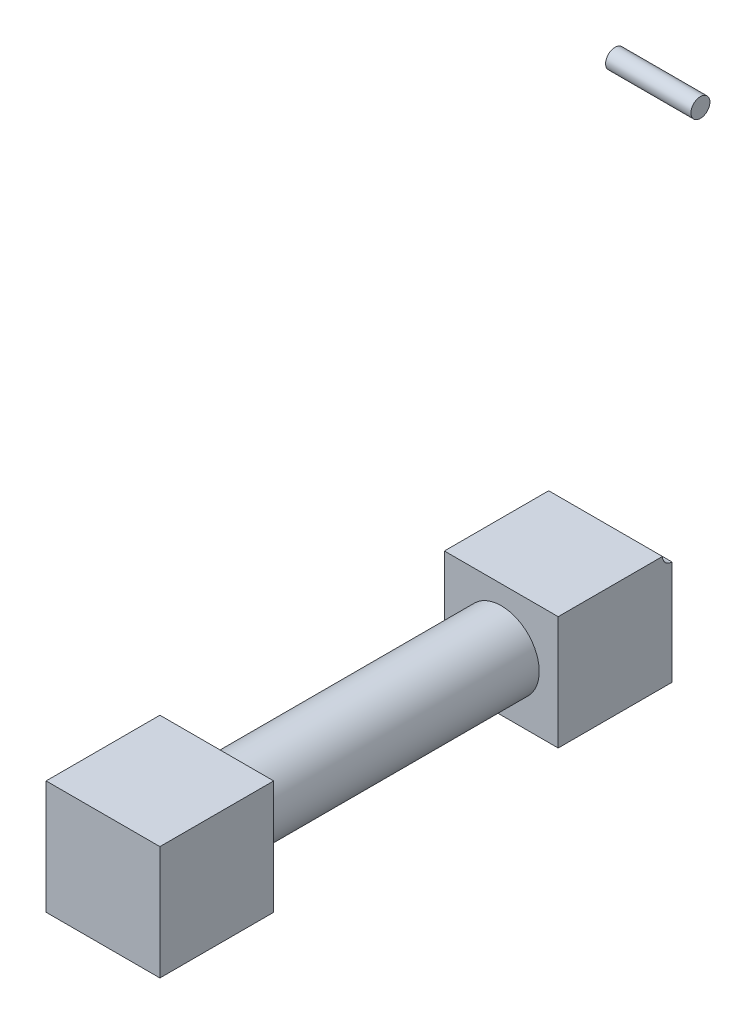
SolidWorks part; units mm, degrees
ref_plane "前视基准面" through (0, 0, 0) normal (0, 0, 1) x (1, 0, 0)
ref_plane "上视基准面" through (0, 0, 0) normal (0, 1, 0) x (1, 0, 0)
ref_plane "右视基准面" through (0, 0, 0) normal (1, 0, 0) x (0, 0, -1)
other "Configuration Table"
sketch "Sketch1" plane through (0, 0, 0) normal (0, 0, 1) x (1, 0, 0)
  line L1 (-30, -30) -> (30, -30)
  line L2 (-30, -30) -> (-30, 30)
  line L3 (-30, 30) -> (30, 30)
  line L4 (30, -30) -> (30, 30)
  line L5 (-30, -30) -> (30, 30) construction
  line L6 (-30, 30) -> (30, -30) construction
  point P0 (0, 0)
extrude "Boss-Extrude1" add sketch "Sketch1" along normal blind 60
ref_plane "Plane1" through (0, 0, 60) normal (0, 0, 1) x (1, 0, 0)
sketch "Sketch2" plane through (0, 0, 60) normal (0, 0, 1) x (1, 0, 0)
  circle A0 centre (0, 0) radius 20
extrude "Boss-Extrude2" add sketch "Sketch2" along normal blind 150
ref_plane "Plane2" through (0, 0, 210) normal (0, 0, 1) x (1, 0, 0)
sketch "Sketch3" plane through (0, 0, 210) normal (0, 0, 1) x (1, 0, 0)
  line L1 (-30, -30) -> (30, -30)
  line L2 (-30, -30) -> (-30, 30)
  line L3 (-30, 30) -> (30, 30)
  line L4 (30, -30) -> (30, 30)
  line L5 (-30, -30) -> (30, 30) construction
  line L6 (-30, 30) -> (30, -30) construction
  point P0 (0, 0)
extrude "Boss-Extrude3" add sketch "Sketch3" along normal blind 60
sketch "Sketch4" plane through (0, 0, 0) normal (1, 0, 0) x (0, 0, -1)
  circle A0 centre (0, 30) radius 5
extrude "Cut-Extrude1" cut sketch "Sketch4" along normal blind 100 and the other way blind 100
sketch "Sketch5" plane through (0, 0, 0) normal (1, 0, 0) x (0, 0, -1)
  circle A0 centre (0, 240) radius 5
sketch "Sketch6" plane through (0, 0, 0) normal (1, 0, 0) x (0, 0, -1)
  circle A0 centre (0, 240) radius 5
extrude "Boss-Extrude4" add sketch "Sketch6" along normal blind 45
ref_plane "bottom_side_face" through (-30, 0, 0) normal (1, 0, 0) x (0, 0, -1)
ref_plane "top_pin_face" through (30, 0, 0) normal (1, 0, 0) x (0, 0, -1)
ref_plane "side_mate_face_top" through (30, 0, 0) normal (1, 0, 0) x (0, 0, -1)
sketch3d "3DSketch1"
  line L0 (-100, 0, 30) -> (100, 0, 30) construction
ref_axis "bottom_hole_axis" through (-100, 0, 30) along (1, 0, 0)
sketch3d "3DSketch2"
  line L0 (-100, 0, 240) -> (100, 0, 240) construction
ref_axis "pin_axis" through (-100, 0, 240) along (1, 0, 0)
